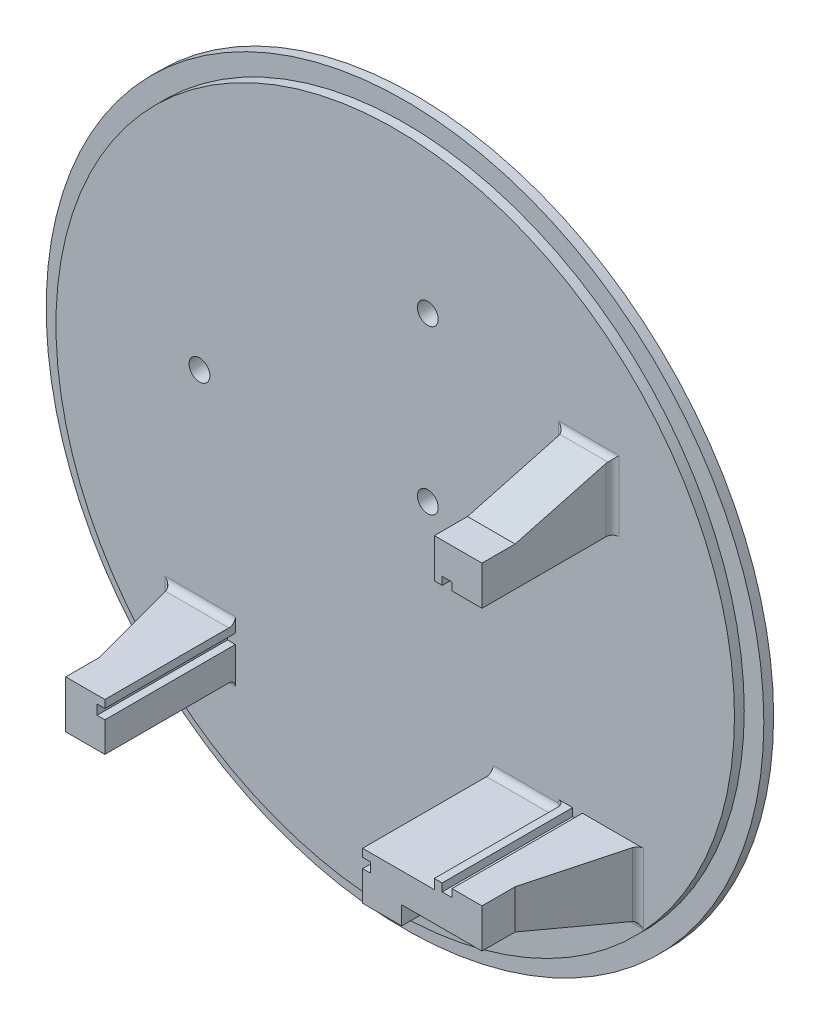
SolidWorks part; units mm, degrees
material "ABS"
ref_plane "Ebene vorne" through (0, 0, 0) normal (0, 0, 1) x (1, 0, 0)
ref_plane "Ebene oben" through (0, 0, 0) normal (0, 1, 0) x (1, 0, 0)
ref_plane "Ebene rechts" through (0, 0, 0) normal (1, 0, 0) x (0, 0, -1)
sketch "Skizze1" plane through (0, 0, 0) normal (0, 0, 1) x (1, 0, 0)
  circle A0 centre (0, 0) radius 55
  circle A1 centre (0, 0) radius 52
  point P15 (0, 0)
  point P23 (0, 0)
  dimension "D1" = 110
  dimension "D2" = 3
extrude "Aufsatz-Linear austragen1" add sketch "Skizze1" along normal blind 3 contours A1 region at (0, 0, 0)
extrude "Aufsatz-Linear austragen2" add sketch "Skizze1<3>" along normal blind 1.5 contours A0 A1 region at (-53.4444, 0, 0)
sketch "Skizze1<3>" plane through (0, 0, 0) normal (0, 0, 1) x (1, 0, 0) same geometry as "Skizze1"
sketch "Skizze2" plane through (0, 0, 3) normal (0, 0, 1) x (1, 0, 0)
  line L0 (25.9967, -4.75) -> (33.2967, -4.75) construction
  line L1 (26, 15) -> (27.2, 15)
  line L2 (26, 15) -> (26, 21)
  line L3 (26, 21) -> (33.3, 21)
  line L4 (33.3, -30.5) -> (33.3, -24.5)
  line L5 (27.2, 15) -> (27.2, 16.2)
  line L6 (27.2, 16.2) -> (28.7, 16.2)
  line L7 (28.7, 16.2) -> (28.7, 15)
  line L8 (28.7, 15) -> (33.3, 15)
  line L9 (28.7, -24.5) -> (33.3, -24.5)
  line L10 (28.7, -25.7) -> (28.7, -24.5)
  line L11 (27.2, -25.7) -> (28.7, -25.7)
  line L12 (27.2, -24.5) -> (27.2, -25.7)
  line L13 (33.3, 21) -> (33.3, 15)
  line L14 (26, -30.5) -> (33.3, -30.5)
  line L15 (26, -24.5) -> (26, -30.5)
  line L16 (26, -24.5) -> (27.2, -24.5)
  line L17 (15, -26) -> (15, -27.2)
  line L18 (15, -26) -> (21, -26)
  line L19 (21, -26) -> (21, -33.3)
  line L20 (-30.5, -33.3) -> (-24.5, -33.3)
  line L21 (15, -27.2) -> (16.2, -27.2)
  line L22 (16.2, -27.2) -> (16.2, -28.7)
  line L23 (16.2, -28.7) -> (15, -28.7)
  line L24 (15, -28.7) -> (15, -33.3)
  line L25 (-24.5, -28.7) -> (-24.5, -33.3)
  line L26 (-25.7, -28.7) -> (-24.5, -28.7)
  line L27 (-25.7, -27.2) -> (-25.7, -28.7)
  line L28 (-24.5, -27.2) -> (-25.7, -27.2)
  line L29 (21, -33.3) -> (15, -33.3)
  line L30 (-30.5, -26) -> (-30.5, -33.3)
  line L31 (-24.5, -26) -> (-30.5, -26)
  line L32 (-24.5, -26) -> (-24.5, -27.2)
  line L33 (-4.75, -25.9967) -> (-4.75, -33.2967) construction
  line L34 (26, -30.5) -> (21, -30.5)
  line L35 (21, -26) -> (26, -26)
  point P1 (0, 0)
  point P41 (0, 0)
  dimension "D1" = 7.3
  dimension "D2" = 1.5
  dimension "D3" = 1.2
  dimension "D4" = 15
  dimension "D5" = 6
  dimension "D6" = 2
  dimension "D7" = 1.2
  dimension "D8" = 19.75
  dimension "D9" = 26
extrude "Aufsatz-Linear austragen5" add sketch "Skizze2" along normal blind 20 contours L29 L19 L18 L17 L21 L22 L23 L24 | L35 L19 L34 L15 | L16 L15 L14 L4 L9 L10 L11 L12 | L13 L3 L2 L1 L5 L6 L7 L8 | L32 L31 L30 L20 L25 L26 L27 L28 region at (29.7229, 18.1029, 3) region at (29.7229, -27.6029, 3) region at (23.5, -28.25, 3) region at (18.1029, -29.7229, 3) region at (-27.6029, -29.7229, 3)
chamfer "Fase2" distance 4 angle 75 4 edges at (33.3, -27.5, 3) (18, -33.3, 3) (29.65, 21, 3) (-30.5, -29.65, 3) first distance on face at (-26.3, -28.8, 3)
chamfer "Fase3" distance 4 angle 75 2 edges at (29.15, -30.5, 3) (21, -33.9, 3) first distance on face at (-27.3, -28.8, 3)
fillet "Verrundung1" radius 1 12 edges at (26, 20, 3) (29.65, 25, 3) (33.3, 20, 3) (-29.5, -33.3, 3) (-34.5, -29.65, 3) (-29.5, -26, 3) (26, -25.25, 3) (20.5, -26, 3) (37.3, -29.5, 3) (31.15, -34.5, 3) (25, -35.9, 3) (20, -37.3, 3)
sketch "Skizze3" plane through (0, 0, 3) normal (0, 0, 1) x (1, 0, 0)
  circle A0 centre (4.995, 4.9959) radius 1.6
  circle A1 centre (4.995, 29.9959) radius 1.6
  circle A2 centre (-30.005, 4.9959) radius 1.6
  dimension "D1" = 3.2
  dimension "D2" = 3.2
  dimension "D3" = 3.2
extrude "Schnitt-Linear austragen1" cut sketch "Skizze3" against normal up to next
